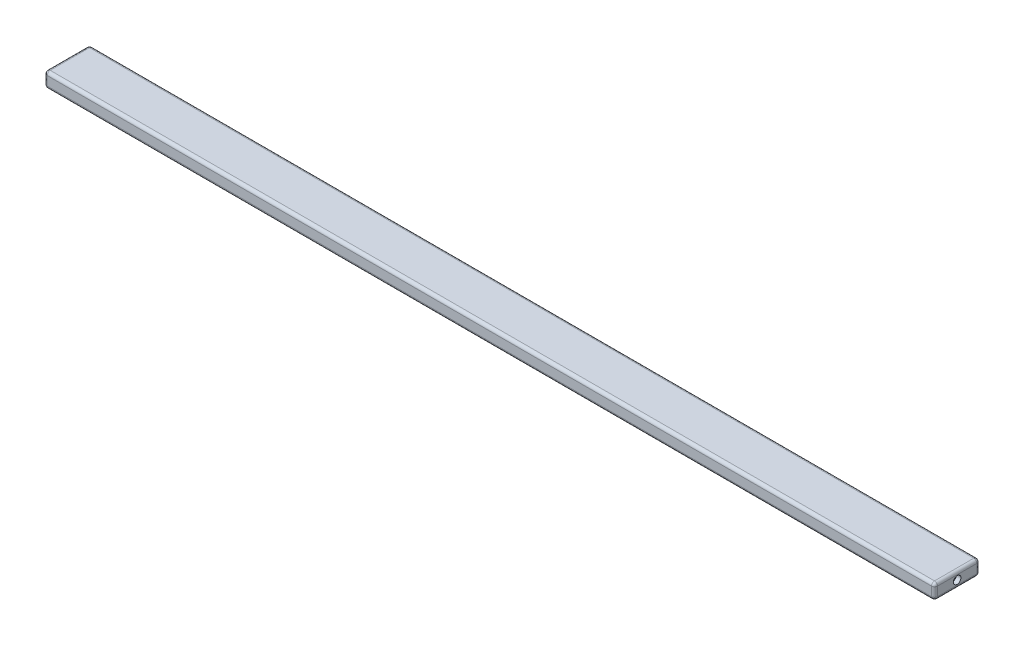
SolidWorks part; units mm, degrees
material "1023 Carbon Steel Sheet (SS)"
ref_plane "Ön Düzlem" through (0, 0, 0) normal (0, 0, 1) x (1, 0, 0)
ref_plane "Üst Düzlem" through (0, 0, 0) normal (0, 1, 0) x (1, 0, 0)
ref_plane "Sağ Düzlem" through (0, 0, 0) normal (1, 0, 0) x (0, 0, -1)
sketch "Sketch1" plane through (0, 0, 0) normal (0, 0, 1) x (1, 0, 0)
  line L0 (-295, 0) -> (295, 0)
  line L1 (295, 0) -> (295, 10)
  line L2 (295, 10) -> (-295, 10)
  line L3 (-295, 10) -> (-295, 0)
  dimension "D1" = 590
  dimension "D2" = 10
extrude "Boss-Extrude1" add sketch "Sketch1" along normal blind 30
fillet "Fillet1" radius 2 11 edges at (-295, 0, 15) (-295, 10, 15) (-295, 5, 30) (-295, 5, 0) (0, 0, 0) (0, 10, 0) (295, 5, 0) (295, 0, 15) (295, 10, 15) (0, 0, 30) (0, 10, 30)
fillet "Fillet2" radius 2 3 edges at (294.4142, 0.5858, 29.4142) (294.4142, 9.4142, 29.4142) (295, 5, 30)
sketch "Sketch5" plane through (-295, 0, 0) normal (-1, 0, 0) x (0, 0, 1)
  line L0 (0, 2) -> (0, 8) construction
  line L1 (2, 10) -> (28, 10) construction
  circle A0 centre (10, 5) radius 2.5
  dimension "D1" = 10
  dimension "D3" = 5
  dimension "D2" = 5
extrude "Cut-Extrude7" cut sketch "Sketch5" against normal blind 3
sketch "Sketch6" plane through (295, 0, 0) normal (1, 0, 0) x (0, 0, -1)
  line L0 (-30, 2) -> (-30, 8) construction
  line L1 (-28, 10) -> (-2, 10) construction
  circle A0 centre (-15, 5) radius 2.5
  point P4 (0, 0)
  point P6 (-14.7737, 4.6605)
  dimension "D1" = 15
  dimension "D3" = 5
  dimension "D2" = 5
extrude "Cut-Extrude8" cut sketch "Sketch6" against normal blind 3
